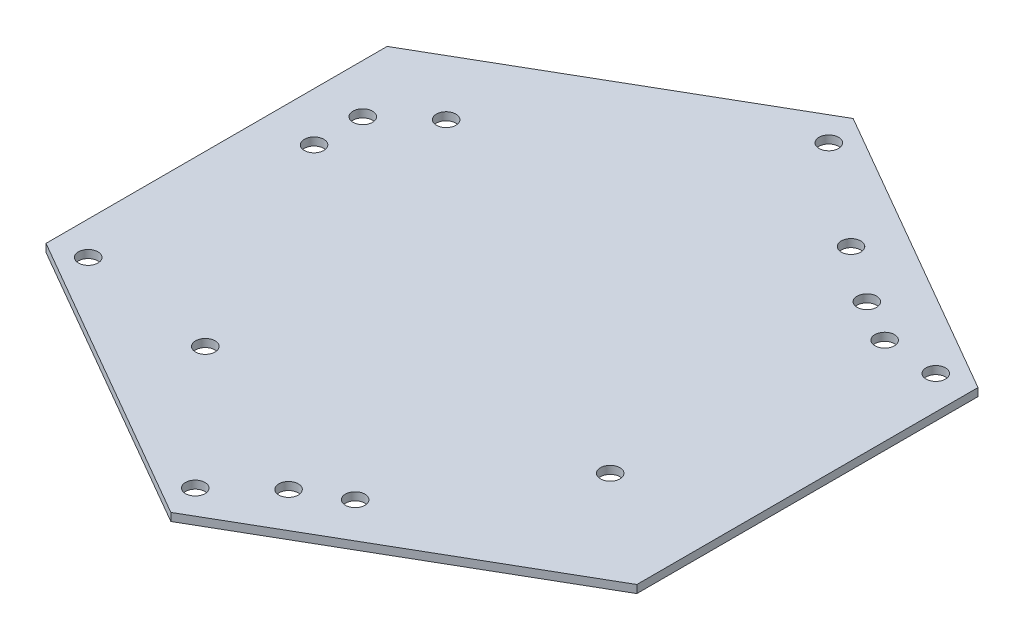
SolidWorks part; units mm, degrees
material "5052-H32"
ref_plane "Front Plane" through (0, 0, 0) normal (0, 0, 1) x (1, 0, 0)
ref_plane "Top Plane" through (0, 0, 0) normal (0, 1, 0) x (1, 0, 0)
ref_plane "Right Plane" through (0, 0, 0) normal (1, 0, 0) x (0, 0, -1)
sketch "Sketch1" plane through (0, 0, 0) normal (0, 1, 0) x (1, 0, 0)
  line L0 (10.1478, -68.3765) -> (21.1463, -62.0265) construction
  line L1 (0, 88.9) -> (-76.9897, 44.45)
  line L2 (-76.9897, 44.45) -> (-76.9897, -44.45)
  line L3 (-76.9897, -44.45) -> (0, -88.9)
  line L4 (0, -88.9) -> (76.9897, -44.45)
  line L5 (76.9897, -44.45) -> (76.9897, 44.45)
  line L6 (76.9897, 44.45) -> (0, 88.9)
  line L7 (21.1463, -62.0265) -> (27.4963, -73.025) construction
  line L8 (-64.2897, 25.4) -> (-64.2897, 12.7) construction
  line L9 (-64.2897, 12.7) -> (-76.9897, 12.7) construction
  line L10 (54.1419, 42.9765) -> (43.1434, 49.3265) construction
  line L11 (43.1434, 49.3265) -> (49.4934, 60.325) construction
  circle A0 centre (0, 0) radius 76.9897 construction
  circle A1 centre (10.1478, -68.3765) radius 2.54
  circle A2 centre (21.1463, -62.0265) radius 2.54
  circle A3 centre (-64.2897, 25.4) radius 2.54
  circle A4 centre (-64.2897, 12.7) radius 2.54
  circle A5 centre (54.1419, 42.9765) radius 2.54
  circle A6 centre (43.1434, 49.3265) radius 2.54
  point P13 (38.4948, -66.675)
  point P28 (0, 0)
  dimension "D2" = 5.08
  dimension "D3" = 12.7
  dimension "D4" = 12.7
  dimension "D1" = 177.8
  dimension "D5" = 12.7
  dimension "D6" = 3
extrude "Boss-Extrude1" add sketch "Sketch1" along normal blind 2.0574
sketch "Sketch2" plane through (0, 2.0574, 0) normal (0, 1, 0) x (1, 0, 0)
  line L1 (17.6188, -76.1634) -> (79.2138, 30.5223) construction
  line L2 (17.6188, -76.1634) -> (-83.5676, -17.7434) construction
  line L3 (-83.5676, -17.7434) -> (-21.9726, 88.9423) construction
  line L4 (79.2138, 30.5223) -> (-21.9726, 88.9423) construction
  line L7 (-76.9897, -44.45) -> (0, -88.9) construction
  circle A0 centre (28.6206, 59.7323) radius 2.54
  circle A1 centre (48.4163, -22.8205) radius 2.54
  circle A2 centre (-52.7701, 35.5995) radius 2.54
  circle A3 centre (-32.9744, -46.9534) radius 2.54
  dimension "D5" = 5.08
  dimension "D1" = 123.19
  dimension "D2" = 116.84
  dimension "D3" = 57.15
  dimension "D4" = 53.34
extrude "Cut-Extrude1" cut sketch "Sketch2" against normal through all
sketch "Sketch3" plane through (0, 2.0574, 0) normal (0, 1, 0) x (1, 0, 0)
  line L0 (-76.9897, -44.45) -> (0, -88.9) construction
  line L1 (-68.3154, -42.1257) -> (-2.3243, -80.2257) construction
  line L2 (-2.3243, -80.2257) -> (68.3154, 42.1257) construction
  line L3 (68.3154, 42.1257) -> (2.3243, 80.2257) construction
  line L4 (2.3243, 80.2257) -> (-68.3154, -42.1257) construction
  line L5 (76.9897, 44.45) -> (0, 88.9) construction
  line L6 (-35.3198, -61.1757) -> (-38.4948, -66.675) construction
  circle A0 centre (-68.3154, -42.1257) radius 2.54
  circle A1 centre (-2.3243, -80.2257) radius 2.54
  circle A2 centre (2.3243, 80.2257) radius 2.54
  circle A3 centre (68.3154, 42.1257) radius 2.54
  dimension "D1" = 5.08
  dimension "D2" = 6.35
  dimension "D3" = 6.35
  dimension "D4" = 76.2
extrude "Cut-Extrude2" cut sketch "Sketch3" against normal through all
